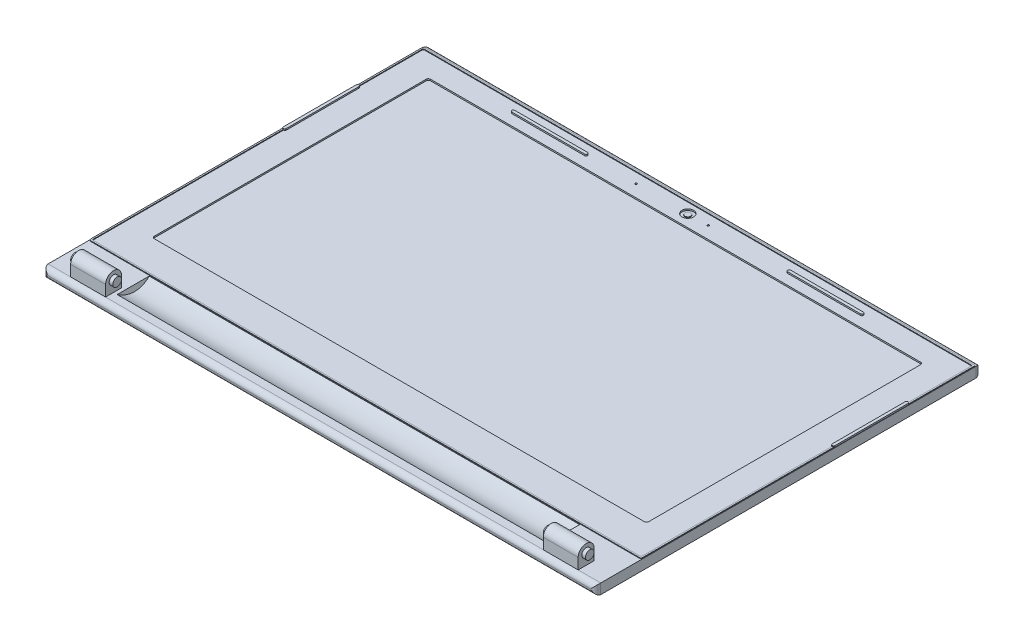
SolidWorks part; units mm, degrees
ref_plane "Front Plane" through (0, 0, 0) normal (0, 0, 1) x (1, 0, 0)
ref_plane "Top Plane" through (0, 0, 0) normal (0, 1, 0) x (1, 0, 0)
ref_plane "Right Plane" through (0, 0, 0) normal (1, 0, 0) x (0, 0, -1)
sketch "Sketch1" plane through (0, 0, 0) normal (0, 1, 0) x (1, 0, 0)
  line L1 (0, 0) -> (380, 0)
  line L2 (0, 0) -> (0, -265)
  line L3 (0, -265) -> (380, -265)
  line L4 (380, 0) -> (380, -265)
  dimension "D1" = 380
  dimension "D2" = 265
extrude "Boss-Extrude1" add sketch "Sketch1" along normal blind 7
fillet "Fillet2" radius 3.5 8 edges at (0, 3.5, 265) (190, 7, 265) (380, 3.5, 265) (190, 0, 265) (380, 3.5, 0) (190, 7, 0) (0, 3.5, 0) (190, 0, 0)
sketch "Sketch2" plane through (0, 7, 0) normal (0, 1, 0) x (1, 0, 0)
  line L0 (380, -261.5) -> (380, -3.5) construction
  line L1 (1.25, -3.75) -> (378.75, -3.75)
  line L2 (0.25, -4.75) -> (0.25, -232.5)
  line L3 (1.25, -233.5) -> (378.75, -233.5)
  line L4 (379.75, -4.75) -> (379.75, -232.5)
  line L5 (380, -3.5) -> (0, -3.5) construction
  line L6 (0, -3.5) -> (0, -261.5) construction
  line L7 (0, -261.5) -> (380, -261.5) construction
  line L8 (2.25, -4.75) -> (377.75, -4.75)
  line L9 (378.75, -5.75) -> (378.75, -231.5)
  line L10 (2.25, -232.5) -> (377.75, -232.5)
  line L11 (1.25, -5.75) -> (1.25, -231.5)
  line L12 (1.25, -4.75) -> (378.75, -4.75) construction
  line L13 (378.75, -4.75) -> (378.75, -232.5) construction
  line L14 (379.75, -3.75) -> (379.75, -233.5) construction
  line L15 (0.25, -3.75) -> (379.75, -3.75) construction
  line L16 (0.25, -233.5) -> (379.75, -233.5) construction
  line L17 (1.25, -232.5) -> (378.75, -232.5) construction
  line L18 (0.25, -3.75) -> (0.25, -233.5) construction
  line L19 (1.25, -4.75) -> (1.25, -232.5) construction
  arc A0 (377.75, -4.75) -> (378.75, -5.75) centre (377.75, -5.75) cw
  arc A1 (379.75, -4.75) -> (378.75, -3.75) centre (378.75, -4.75) ccw
  arc A2 (378.75, -233.5) -> (379.75, -232.5) centre (378.75, -232.5) ccw
  arc A3 (377.75, -232.5) -> (378.75, -231.5) centre (377.75, -231.5) ccw
  arc A4 (1.25, -233.5) -> (0.25, -232.5) centre (1.25, -232.5) cw
  arc A5 (2.25, -232.5) -> (1.25, -231.5) centre (2.25, -231.5) cw
  arc A6 (2.25, -4.75) -> (1.25, -5.75) centre (2.25, -5.75) ccw
  arc A7 (1.25, -3.75) -> (0.25, -4.75) centre (1.25, -4.75) ccw
  dimension "D6" = 1
  dimension "D1" = 0.25
  dimension "D2" = 0.25
  dimension "D3" = 0.25
  dimension "D4" = 28
  dimension "D5" = 1
extrude "Boss-Extrude2" add sketch "Sketch2" along normal blind 0.5
sketch "Sketch3" plane through (0, 7, 0) normal (0, 1, 0) x (1, 0, 0)
  line L0 (0, -3.5) -> (0, -261.5) construction
  line L1 (21.5, -20) -> (358.5, -20)
  line L2 (20, -21.5) -> (20, -208.5)
  line L3 (21.5, -210) -> (358.5, -210)
  line L4 (360, -21.5) -> (360, -208.5)
  line L5 (3.5, 0) -> (376.5, 0) construction
  arc A0 (21.5, -210) -> (20, -208.5) centre (21.5, -208.5) cw
  arc A1 (358.5, -210) -> (360, -208.5) centre (358.5, -208.5) ccw
  arc A2 (360, -21.5) -> (358.5, -20) centre (358.5, -21.5) ccw
  arc A3 (21.5, -20) -> (20, -21.5) centre (21.5, -21.5) ccw
  point P10 (20, -210)
  point P13 (360, -210)
  point P16 (360, -20)
  dimension "D5" = 1.5
  dimension "D1" = 340
  dimension "D2" = 190
  dimension "D3" = 20
  dimension "D4" = 20
extrude "Cut-Extrude1" cut sketch "Sketch3" against normal blind 1
sketch "Sketch4" plane through (0, 7, 0) normal (0, 1, 0) x (1, 0, 0)
  circle A0 centre (190, -11.5849) radius 4
extrude "Cut-Extrude2" cut sketch "Sketch4" against normal blind 1
sketch "Sketch5" plane through (0, 7, 0) normal (0, 1, 0) x (1, 0, 0)
  circle A0 centre (154.3766, -11.5849) radius 0.625
  dimension "D1" = 1.25
extrude "Cut-Extrude3" cut sketch "Sketch5" against normal blind 1
sketch "Sketch6" plane through (0, 7, 0) normal (0, 1, 0) x (1, 0, 0)
  circle A0 centre (204.1097, -11.5849) radius 0.625
  dimension "D1" = 1.25
extrude "Cut-Extrude4" cut sketch "Sketch6" against normal blind 1
sketch "Sketch7" plane through (0, 7, 0) normal (0, 1, 0) x (1, 0, 0)
  line L0 (0, -261.5) -> (380, -261.5) construction
  line L1 (15.5, -261.5) -> (39.5, -261.5)
  line L2 (15.5, -261.5) -> (15.5, -250.5202)
  line L3 (15.5, -250.5202) -> (39.5, -250.5202)
  line L4 (39.5, -261.5) -> (39.5, -250.5202)
  line L5 (0, -3.5) -> (0, -261.5) construction
  dimension "D1" = 15.5
  dimension "D2" = 24
extrude "Boss-Extrude3" add sketch "Sketch7" along normal blind 13
sketch "Sketch8" plane through (15.5, 0, 0) normal (-1, 0, 0) x (0, 0, 1)
  line L0 (250.5202, 20) -> (261.5, 20) construction
  line L1 (250.5202, 14.5101) -> (250.5202, 20)
  line L2 (250.5202, 20) -> (261.5, 20)
  line L3 (261.5, 20) -> (261.5, 14.5101)
  arc A0 (261.5, 14.5101) -> (250.5202, 14.5101) centre (256.0101, 14.5101) ccw
  line M2 (261.5, 7) -> (261.5, 20)
  line M3 (261.5, 20) -> (250.5202, 20)
  line M4 (250.5202, 20) -> (250.5202, 7)
extrude "Cut-Extrude6" cut sketch "Sketch8" against normal blind 27 contours A0 L2 M4 | A0 M2 M3 region at (15.5, 18.7737, 260.2737) region at (15.5, 18.7737, 251.7465)
sketch "Sketch9" plane through (15.5, 0, 0) normal (-1, 0, 0) x (0, 0, 1)
  circle A0 centre (256.0101, 14.5101) radius 3
extrude "Boss-Extrude4" add sketch "Sketch9" along normal blind 2.5
sketch "Sketch10" plane through (39.5, 0, 0) normal (1, 0, 0) x (0, 0, -1)
  circle A0 centre (-256.0101, 14.5101) radius 3
  dimension "D1" = 6
extrude "Boss-Extrude5" add sketch "Sketch10" along normal blind 2.5
sketch "Sketch11" plane through (0, 7, 0) normal (0, 1, 0) x (1, 0, 0)
  line L0 (39.5, -261.5) -> (380, -261.5) construction
  line L1 (364.5, -261.5) -> (340.5, -261.5)
  line L2 (364.5, -261.5) -> (364.5, -250.52)
  line L3 (364.5, -250.52) -> (340.5, -250.52)
  line L4 (340.5, -261.5) -> (340.5, -250.52)
  line L5 (380, -261.5) -> (380, -3.5) construction
  dimension "D1" = 15.5
  dimension "D2" = 24
  dimension "D3" = 10.98
extrude "Boss-Extrude6" add sketch "Sketch11" along normal blind 13
sketch "Sketch15" plane through (0, 7, 0) normal (0, 1, 0) x (1, 0, 0)
  line L0 (0, -3.5) -> (0, -261.5) construction
  point P0 (42, -250.8127)
  dimension "D1" = 42
ref_plane "Plane1" through (42, 0, 0) normal (1, 0, 0) x (0, 0, -1)
sketch "Sketch20" plane through (0, 0, 250.52) normal (0, 0, -1) x (-1, 0, 0)
sketch "Sketch21" plane through (364.5, 0, 0) normal (1, 0, 0) x (0, 0, -1)
  line L0 (-261.5, 20) -> (-250.52, 20) construction
  line L2 (-261.5, 14.51) -> (-261.5, 20)
  line L3 (-261.5, 20) -> (-250.52, 20)
  line L4 (-250.52, 20) -> (-250.52, 14.51)
  arc A0 (-250.52, 14.51) -> (-261.5, 14.51) centre (-256.01, 14.51) ccw
  line M2 (-250.52, 7) -> (-250.52, 20)
  line M3 (-250.52, 20) -> (-261.5, 20)
  line M4 (-261.5, 20) -> (-261.5, 7)
extrude "Cut-Extrude9" cut sketch "Sketch21" against normal blind 296 contours A0 M2 M3 | A0 L3 M4 region at (364.5, 18.7737, 251.7463) region at (364.5, 18.7737, 260.2737)
sketch "Sketch22" plane through (364.5, 0, 0) normal (1, 0, 0) x (0, 0, -1)
  circle A0 centre (-256.01, 14.51) radius 3
extrude "Boss-Extrude7" add sketch "Sketch22" along normal blind 2.5
sketch "Sketch23" plane through (340.5, 0, 0) normal (-1, 0, 0) x (0, 0, 1)
  circle A0 centre (256.01, 14.51) radius 3
extrude "Boss-Extrude8" add sketch "Sketch23" along normal blind 2.5
sketch "Sketch25" plane through (15.5, 0, 0) normal (-1, 0, 0) x (0, 0, 1)
sketch "Sketch26" plane through (0, 7, 0) normal (0, 1, 0) x (1, 0, 0)
sketch "Sketch29" plane through (0, 7, 0) normal (0, 1, 0) x (1, 0, 0)
  line L0 (44.3028, -256.0101) -> (44.3028, -235.0101)
sketch "Sketch31" plane through (42, 0, 0) normal (1, 0, 0) x (0, 0, -1)
  line L0 (-256.0101, 7) -> (-234.0101, 7)
  line L1 (-256.0101, 7) -> (-235.0101, 7) construction
  arc A0 (-256.0101, 7) -> (-234.0101, 7) centre (-245.0101, 24.8885) ccw
extrude "Cut-Extrude10" cut sketch "Sketch31" along normal blind 296
draft "Draft1" type of draft neutral plane draft angle 20 faces to draft 1 face at (338, 5.4443, 245.0101) neutral plane through (0, 7, 0) neutral plane normal (0, 1, 0) parameters "D1"=20
draft "Draft2" type of draft neutral plane draft angle 20 faces to draft 1 face at (42, 5.4443, 245.0101) neutral plane through (0, 7, 0) neutral plane normal (0, 1, 0) parameters "D1"=20
sketch "Sketch32" plane through (0, 7, 0) normal (0, 1, 0) x (1, 0, 0)
  line L0 (70, -11.5849) -> (120, -11.5849) construction
  line L1 (70, -10.5849) -> (120, -10.5849)
  line L2 (70, -12.5849) -> (120, -12.5849)
  line L3 (0, -3.5) -> (0, -261.5) construction
  line L4 (260, -11.8811) -> (310, -11.8811) construction
  line L5 (260, -10.8811) -> (310, -10.8811)
  line L6 (260, -12.8811) -> (310, -12.8811)
  line L7 (380, -261.5) -> (380, -3.5) construction
  line L8 (1.25, -50) -> (1.25, -100) construction
  line L9 (1.25, -5.75) -> (1.25, -231.5) construction
  line L10 (2.25, -50) -> (2.25, -100)
  line L11 (0.25, -50) -> (0.25, -100)
  line L13 (3.5, 0) -> (376.5, 0) construction
  line L14 (378.75, -50) -> (378.75, -100) construction
  line L15 (378.75, -231.5) -> (378.75, -5.75) construction
  line L16 (379.75, -50) -> (379.75, -100)
  line L17 (377.75, -50) -> (377.75, -100)
  arc A0 (70, -10.5849) -> (70, -12.5849) centre (70, -11.5849) ccw
  arc A1 (120, -12.5849) -> (120, -10.5849) centre (120, -11.5849) ccw
  arc A2 (260, -10.8811) -> (260, -12.8811) centre (260, -11.8811) ccw
  arc A3 (310, -12.8811) -> (310, -10.8811) centre (310, -11.8811) ccw
  arc A4 (2.25, -50) -> (0.25, -50) centre (1.25, -50) ccw
  arc A5 (0.25, -100) -> (2.25, -100) centre (1.25, -100) ccw
  arc A6 (379.75, -50) -> (377.75, -50) centre (378.75, -50) ccw
  arc A7 (377.75, -100) -> (379.75, -100) centre (378.75, -100) ccw
  point P3 (95, -11.5849)
  point P12 (285, -11.8811)
  point P23 (1.25, -75)
  point P34 (378.75, -75)
  dimension "D1" = 2
  dimension "D2" = 50
  dimension "D3" = 70
  dimension "D4" = 50
  dimension "D5" = 2
  dimension "D6" = 70
  dimension "D7" = 50
  dimension "D8" = 2
  dimension "D9" = 50
  dimension "D10" = 2
  dimension "D11" = 50
  dimension "D12" = 50
extrude "Boss-Extrude9" add sketch "Sketch32" along normal blind 1
sketch "Sketch33" plane through (0, 6, 0) normal (0, 1, 0) x (1, 0, 0)
  circle A0 centre (190, -11.5849) radius 2
extrude "Boss-Extrude10" add sketch "Sketch33" along normal blind 0.5
sketch "Sketch34" plane through (0, 6, 0) normal (0, 1, 0) x (1, 0, 0)
  line L0 (234.3333, 384) -> (1171.6667, 384) construction
sketch "Sketch35" plane through (0, 6, 0) normal (0, 1, 0) x (1, 0, 0)
  line L0 (20, -208.5) -> (360, -208.5) construction
